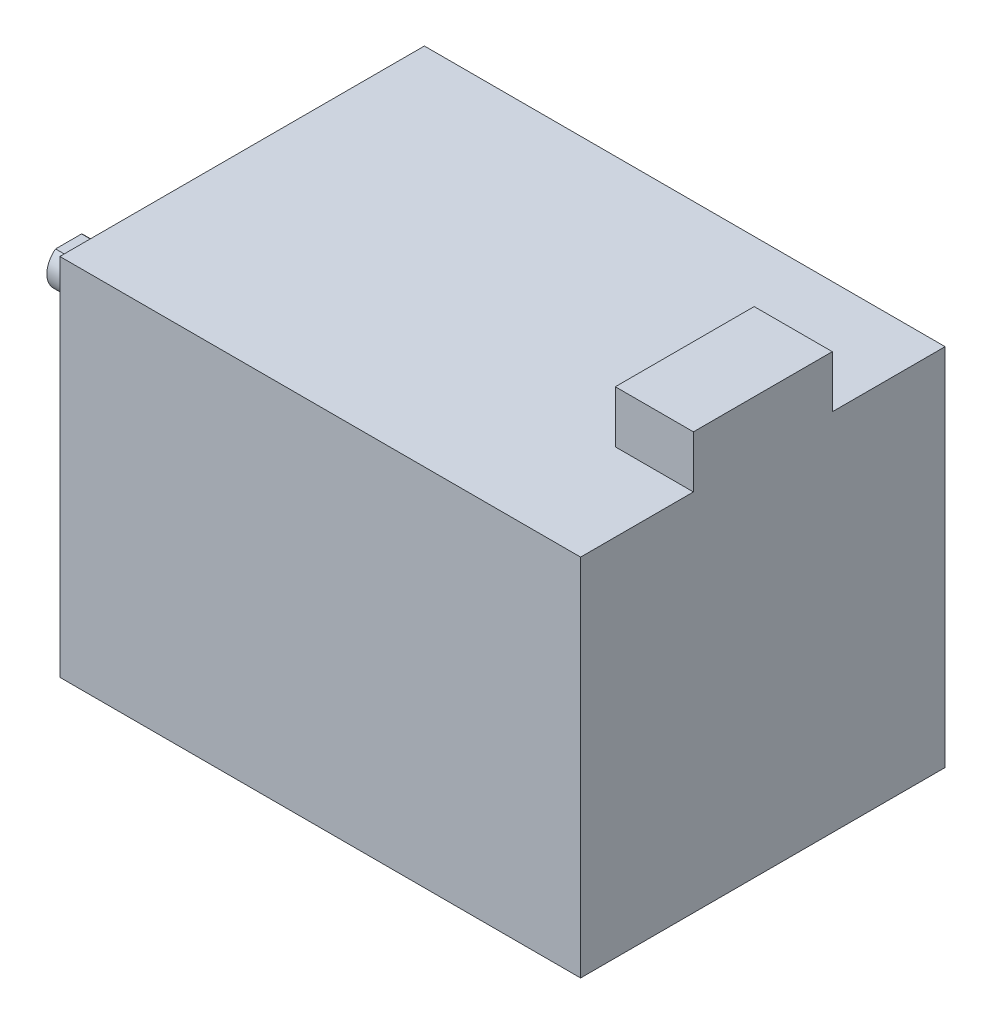
SolidWorks part; units mm, degrees
ref_plane "前视基准面" through (0, 0, 0) normal (0, 0, 1) x (1, 0, 0)
ref_plane "上视基准面" through (0, 0, 0) normal (0, 1, 0) x (1, 0, 0)
ref_plane "右视基准面" through (0, 0, 0) normal (1, 0, 0) x (0, 0, -1)
sketch "草图2" plane through (0, 0, 0) normal (1, 0, 0) x (0, 0, -1)
  line L0 (23.1, 0) -> (-23.1, 0) construction
  line L1 (-21, -21) -> (21, -21)
  line L2 (-21, -21) -> (-21, 21)
  line L3 (-21, 21) -> (21, 21)
  line L4 (21, -21) -> (21, 21)
  line L5 (-21, -21) -> (21, 21) construction
  line L6 (-21, 21) -> (21, -21) construction
  line L7 (-15.5, -15.5) -> (15.5, -15.5) construction
  line L8 (-15.5, -15.5) -> (-15.5, 15.5) construction
  line L9 (-15.5, 15.5) -> (15.5, 15.5) construction
  line L10 (15.5, -15.5) -> (15.5, 15.5) construction
  line L11 (-15.5, -15.5) -> (15.5, 15.5) construction
  line L12 (-15.5, 15.5) -> (15.5, -15.5) construction
  line L13 (0, 26.4) -> (0, -26.4) construction
  line L14 (-1.5, 2) -> (1.5, 2)
  line L15 (-8, 21) -> (8, 21)
  line L16 (-8, 21) -> (-8, 27)
  line L17 (-8, 27) -> (8, 27)
  line L18 (8, 21) -> (8, 27)
  circle A0 centre (15.5, 15.5) radius 1.5
  circle A1 centre (15.5, -15.5) radius 1.5
  circle A2 centre (-15.5, -15.5) radius 1.5
  circle A3 centre (-15.5, 15.5) radius 1.5
  arc A4 (-1.5, 2) -> (1.5, 2) centre (0, 0) ccw
  point P0 (0, 0)
  point P6 (0, 0)
  dimension "D5" = 3
  dimension "D9" = 5
  dimension "D1" = 42
  dimension "D2" = 42
  dimension "D3" = 31
  dimension "D4" = 31
  dimension "D6" = 6
  dimension "D7" = 16
  dimension "D8" = 13
  dimension "D10" = 2
extrude "凸台-拉伸1" add sketch "草图2" along normal blind 60 contours L14 A4 | L1 L4 L3 L2 A4 L14 A1 A0 A2 A3 region at (0, 0, 20.406) region at (0, -0.1209, 0)
extrude "凸台-拉伸2" add sketch "草图2<3>" against normal blind 20 contours L14 A4 region at (0, -0.1209, 0)
sketch "草图2<3>" plane through (0, 0, 0) normal (1, 0, 0) x (0, 0, -1) same geometry as "草图2"
extrude "凸台-拉伸3" add sketch "草图2<4>" along normal blind 60 contours L3 L18 L17 L16 region at (0, 24, 0)
sketch "草图2<4>" plane through (0, 0, 0) normal (1, 0, 0) x (0, 0, -1) same geometry as "草图2"
extrude "切除-拉伸1" cut sketch "草图2<5>" along normal blind 51 contours L3 L18 L17 L16 region at (0, 24, 0)
sketch "草图2<5>" plane through (0, 0, 0) normal (1, 0, 0) x (0, 0, -1) same geometry as "草图2"
extrude "凸台-拉伸4" add sketch "草图2<6>" along normal blind 60 contours A0 | A1 | A3 | A2 region at (0, 15.5, -15.5) region at (0, -15.5, -15.5) region at (0, -15.5, 15.5) region at (0, 15.5, 15.5)
sketch "草图2<6>" plane through (0, 0, 0) normal (1, 0, 0) x (0, 0, -1) same geometry as "草图2"
extrude "切除-拉伸2" cut sketch "草图2<7>" along normal blind 10 contours A2 | A3 | A0 | A1 region at (0, 15.5, -15.5) region at (0, -15.5, -15.5) region at (0, -15.5, 15.5) region at (0, 15.5, 15.5)
sketch "草图2<7>" plane through (0, 0, 0) normal (1, 0, 0) x (0, 0, -1) same geometry as "草图2"
